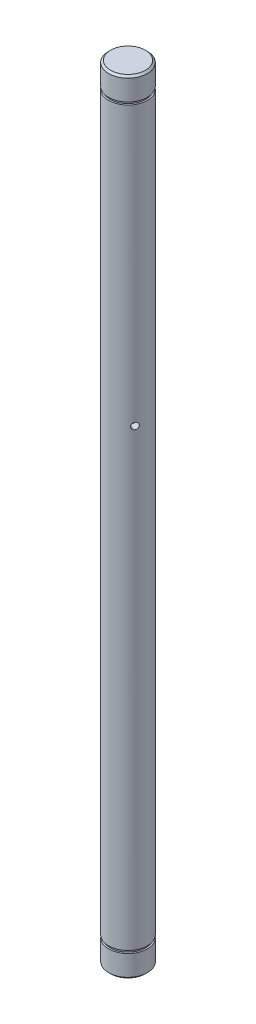
SolidWorks part; units mm, degrees
material "Chromed steel"
ref_plane "Piano frontale" through (0, 0, 0) normal (0, 0, 1) x (1, 0, 0)
ref_plane "Piano superiore" through (0, 0, 0) normal (0, 1, 0) x (1, 0, 0)
ref_plane "Piano destro" through (0, 0, 0) normal (1, 0, 0) x (0, 0, -1)
sketch "Schizzo1" plane through (0, 0, 0) normal (0, 1, 0) x (1, 0, 0)
  circle A0 centre (0, 0) radius 30
  dimension "D1" = 60
extrude "Estrusione1" add sketch "Schizzo1" along normal blind 1136
sketch "Schizzo2" plane through (0, 1136, 0) normal (0, 1, 0) x (1, 0, 0)
  circle A0 centre (0, 0) radius 27.5
extrude "Estrusione2" add sketch "Schizzo2" along normal blind 4
sketch "Schizzo3" plane through (0, 1140, 0) normal (0, 1, 0) x (1, 0, 0)
  circle A0 centre (0, 0) radius 30
extrude "Estrusione3" add sketch "Schizzo3" along normal blind 35
cosmetic thread "Filettatura cosmetica3" parameters "D2"=53.971
chamfer "Smusso1" distance 3 angle 45 1 edges at (0, 1175, 30)
sketch "Schizzo4" plane through (0, 0, 0) normal (0, -1, 0) x (1, 0, 0)
  circle A0 centre (0, 0) radius 27.5
extrude "Estrusione4" add sketch "Schizzo4" along normal blind 4
sketch "Schizzo5" plane through (0, -4, 0) normal (0, -1, 0) x (1, 0, 0)
  circle A0 centre (0, 0) radius 30
extrude "Estrusione5" add sketch "Schizzo5" along normal blind 35
cosmetic thread "Filettatura cosmetica2" parameters "D2"=56
chamfer "Smusso2" distance 3 angle 45 1 edges at (0, -39, -30)
sketch "Schizzo6" plane through (0, 0, 0) normal (0, 0, 1) x (1, 0, 0)
  line L0 (27, 1175) -> (-27, 1175) construction
  circle A0 centre (0, 704) radius 5
  dimension "D1" = 10
  dimension "D2" = 471
extrude "Estrusione6" cut sketch "Schizzo6" against normal through all from offset 18 offset against normal yes
pattern_circular "RipetizioneCircolare1" count 3 over 360 about axis through (0, 1136, 0) along (0, -1, 0) of "Estrusione6"
ref_axis "Assi1" through (0, 1136, 0) along (0, -1, 0)
ref_plane "Piano1" through (0, 568, 0) normal (0, -1, 0) x (-1, 0, 0)
